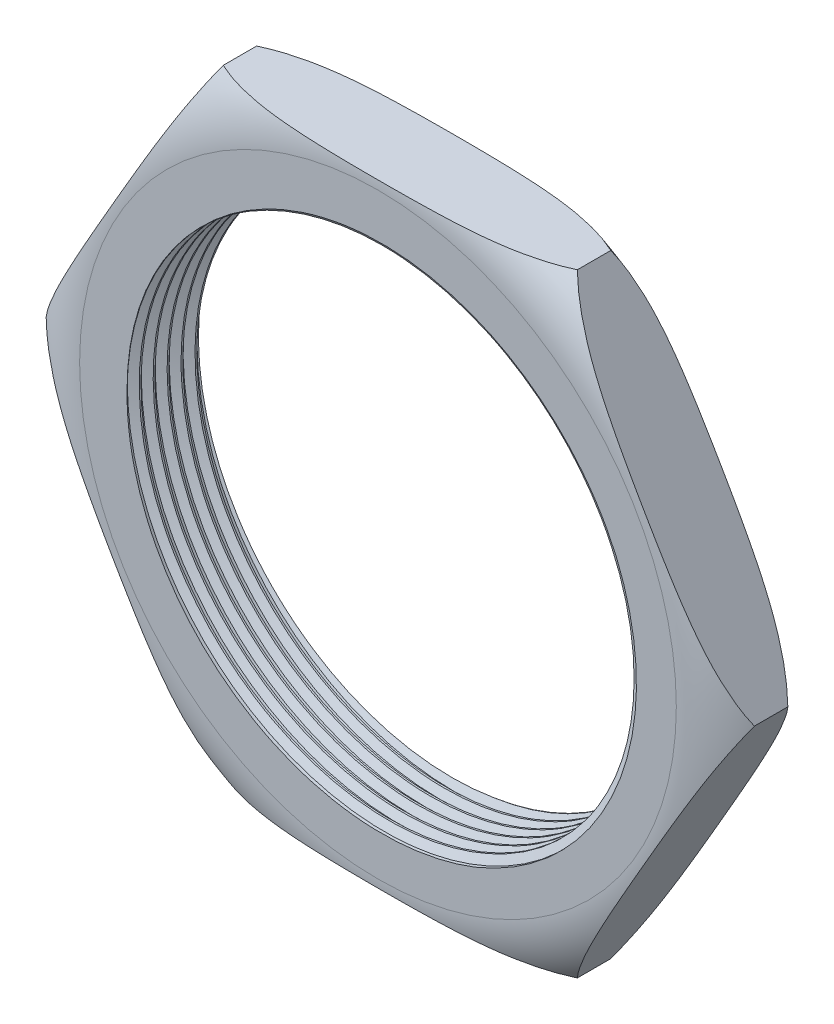
SolidWorks part; units mm, degrees
ref_plane "Front Plane" through (0, 0, 0) normal (0, 0, 1) x (1, 0, 0)
ref_plane "Top Plane" through (0, 0, 0) normal (0, 1, 0) x (1, 0, 0)
ref_plane "Right Plane" through (0, 0, 0) normal (1, 0, 0) x (0, 0, -1)
sketch "Sketch1" plane through (0, 0, 0) normal (0, 0, 1) x (1, 0, 0)
  line L1 (6.3509, -11) -> (12.7017, 0)
  line L2 (12.7017, 0) -> (6.3509, 11)
  line L3 (6.3509, 11) -> (-6.3509, 11)
  line L4 (-6.3509, 11) -> (-12.7017, 0)
  line L5 (-12.7017, 0) -> (-6.3509, -11)
  line L6 (-6.3509, -11) -> (6.3509, -11)
  circle A0 centre (0, 0) radius 11 construction
  dimension "D1" = 22
extrude "Boss-Extrude1" add sketch "Sketch1" along normal blind 2.8
sketch "Sketch2" plane through (0, 0, 2.8) normal (0, 0, 1) x (1, 0, 0)
  circle A0 centre (0, 0) radius 9
  dimension "D1" = 18
extrude "Cut-Extrude1" cut sketch "Sketch2" against normal up to next
sketch "Sketch3" plane through (0, 0, 0) normal (0, 1, 0) x (1, 0, 0)
  line L0 (-12.7017, -0.8) -> (-12.7017, 0)
  line L1 (-12.7017, -2.8) -> (-12.7017, 0) construction
  line L2 (-12.7017, 0) -> (-10.7017, 0)
  line L3 (-6.3509, 0) -> (-12.7017, 0) construction
  line L4 (-12.7017, -2) -> (-12.7017, -2.8)
  line L5 (-12.7017, -2.8) -> (-10.7017, -2.8)
  line L6 (-6.3509, -2.8) -> (-12.7017, -2.8) construction
  line L7 (0, 0) -> (0, -2.8) construction
  line L8 (6.3509, -2.8) -> (-6.3509, -2.8) construction
  arc A0 (-10.7017, 0) -> (-12.7017, -0.8) centre (-10.7017, -2.9) ccw
  arc A1 (-10.7017, -2.8) -> (-12.7017, -2) centre (-10.7017, 0.1) cw
  dimension "D1" = 2
  dimension "D2" = 1.2
revolve "Cut-Revolve1" cut sketch "Sketch3" angle 360 about L7
thread "Thread1" pitch 0.5 method cut profile "Thread Profile1" start angle 0, offset 1, length 0, pitch 0.5, diameter 18
ref_plane "Plane1" through (-9, 0, 3.8) normal (0, 1, 0) x (1, 0, 0)
sketch "Thread Profile1" plane through (-9, 0, 3.8) normal (0, 1, 0) x (1, 0, 0)
  line L0 (0, 0) -> (0, 0.5) construction
  line L11 (0, 0) -> (0, 0.4375)
  line L12 (0, 0.4375) -> (-0.2706, 0.2812)
  line L13 (-0.2706, 0.2812) -> (-0.2706, 0.1562)
  line L15 (-0.2706, 0.1562) -> (0, 0)
  line L17 (-0.2706, 0.2187) -> (0, 0.2187) construction
  point P2 (0, 0)
  dimension "Pitch" = 0.5
  dimension "Profile_Angle" = 60
  dimension "Profile_Land" = 0.125
  dimension "Profile_Height" = 0.2706
